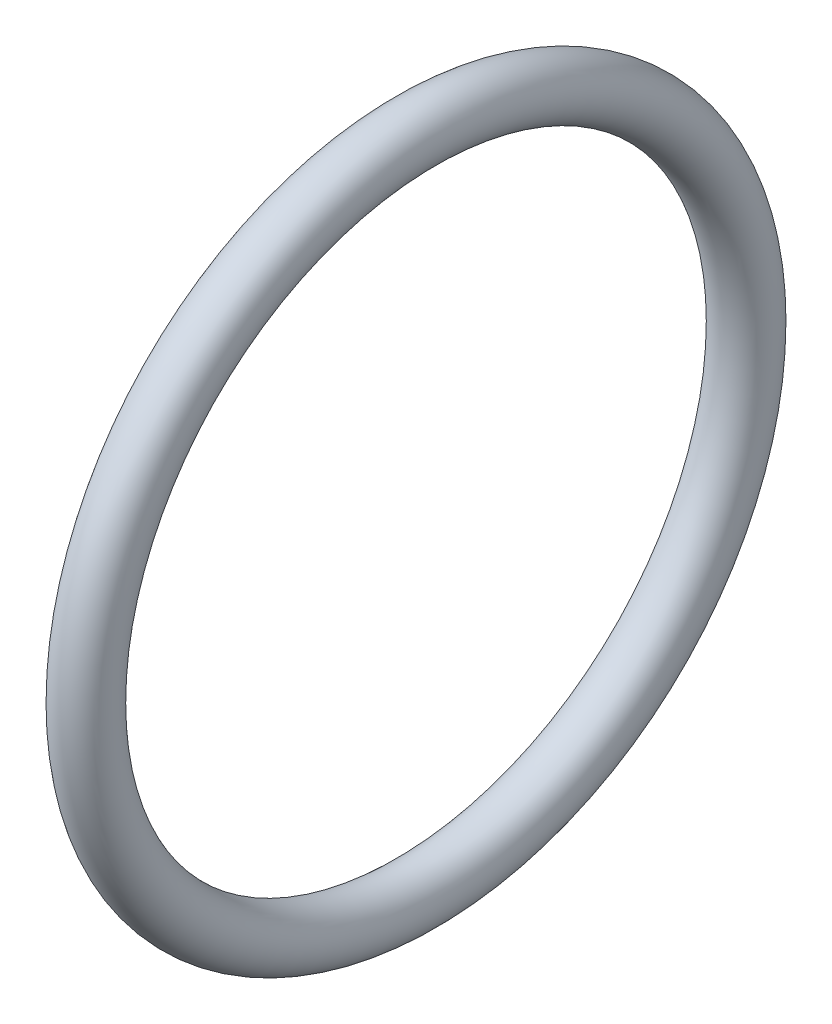
SolidWorks part; units mm, degrees
ref_plane "Front Plane" through (0, 0, 0) normal (0, 0, 1) x (1, 0, 0)
ref_plane "Top Plane" through (0, 0, 0) normal (0, 1, 0) x (1, 0, 0)
ref_plane "Right Plane" through (0, 0, 0) normal (1, 0, 0) x (0, 0, -1)
sketch "Sketch2" plane through (0, 0, 0) normal (0, 0, 1) x (1, 0, 0)
  line L0 (0, 0) -> (58.591, 0) construction
  line L2 (0, 0) -> (18.4, 0)
  line L3 (0, 0) -> (0, 2.5)
  line L4 (0, 2.5) -> (18.4, 2.5)
  line L5 (18.4, 0) -> (18.4, 2.5)
  line L6 (6, 2.5) -> (6, 6)
  line L11 (6, 6) -> (9.97, 6)
  line L16 (12.97, 6) -> (12.97, 3)
  line L17 (12.97, 3) -> (13.6304, 3)
  line L18 (13.6304, 3) -> (13.6304, 2.5)
  line L19 (13.6304, 2.5) -> (6, 2.5)
  line L22 (13.6304, 2.5) -> (16.1104, 2.5)
  line L23 (13.6304, 2.5) -> (13.6304, 4)
  line L24 (13.6304, 4) -> (16.1104, 4)
  line L25 (16.1104, 2.5) -> (16.1104, 4)
  line L27 (6, 6) -> (9.97, 6)
  line L28 (6, 6) -> (6, 9)
  line L29 (6, 9) -> (9.97, 9)
  line L30 (9.97, 6) -> (9.97, 9)
  line L31 (6, 9) -> (6, 8.25)
  line L32 (6, 8.25) -> (5, 8.25)
  line L33 (8.58, 22.001) -> (8.58, 12.476) construction
  line L34 (5, 12.476) -> (12.16, 12.476)
  line L35 (9.97, 9) -> (12.16, 9)
  line L36 (5, 7.5) -> (3, 7.5)
  line L37 (5, 8.25) -> (5, 12.476)
  line L38 (5, 7.5) -> (5, 14)
  line L39 (5, 14) -> (3, 14)
  line L40 (3, 7.5) -> (3, 14)
  line L41 (5, 22.001) -> (12.16, 22.001)
  line L42 (5, 22.001) -> (5, 30.1625)
  line L43 (5, 30.1625) -> (12.16, 30.1625)
  line L44 (12.16, 22.001) -> (12.16, 30.1625)
  line L49 (16.6304, 22.001) -> (16.6304, 7.5)
  line L51 (23.0104, 7.5) -> (23.0104, 6.5)
  line L54 (16.1104, 4) -> (13.6304, 4)
  line L56 (18.0304, 7.5) -> (23.0104, 7.5)
  line L57 (13.16, 22.001) -> (16.6304, 22.001)
  line L58 (16.1104, 3.5) -> (20.0104, 3.5)
  line L59 (29.9004, 14) -> (26.9004, 11)
  line L60 (4, 31.75) -> (18.0304, 31.75)
  line L61 (18.0304, 7.5) -> (23.0104, 7.5)
  line L62 (18.0304, 7.5) -> (18.0304, 12)
  line L63 (18.0304, 12) -> (23.0104, 12)
  line L64 (23.0104, 7.5) -> (23.0104, 12)
  line L65 (18.0304, 31.75) -> (18.0304, 12)
  line L66 (23.0104, 11) -> (26.9004, 11)
  line L67 (34.8004, 23) -> (31.3004, 19.5)
  line L68 (35.8004, 31) -> (38.7904, 33.99)
  line L69 (29.9004, 14) -> (29.9004, 15)
  line L70 (29.9004, 15) -> (22.9304, 15)
  line L71 (22.9304, 15) -> (21.0304, 15)
  line L72 (18.0304, 7.5) -> (16.6304, 7.5)
  line L73 (21.0304, 15) -> (21.0304, 43)
  line L74 (20.0304, 40) -> (10.0704, 40)
  line L75 (10.0704, 40) -> (4, 40)
  line L76 (21.0304, 43) -> (20.0304, 43)
  line L77 (22.9304, 15) -> (29.9004, 15)
  line L78 (22.9304, 15) -> (22.9304, 21)
  line L79 (22.9304, 21) -> (29.9004, 21)
  line L80 (29.9004, 15) -> (29.9004, 21)
  line L81 (10.0704, 40) -> (20.0304, 40)
  line L82 (10.0704, 40) -> (10.0704, 50)
  line L83 (10.0704, 50) -> (20.0304, 50)
  line L84 (20.0304, 40) -> (20.0304, 50)
  line L85 (4, 40) -> (4, 31.75)
  line L86 (12.97, 3) -> (12.97, 2.5)
  line L87 (31.3004, 19.5) -> (29.9004, 19.5)
  line L88 (21.51, 63.5) -> (21.51, 44)
  line L89 (21.51, 63.5) -> (25.9304, 63.5)
  line L90 (25.9304, 63.5) -> (25.9304, 25)
  line L91 (27.8304, 25) -> (25.9304, 25)
  line L92 (10.0704, 48) -> (9, 48)
  line L93 (9, 48) -> (9, 53.476)
  line L94 (9, 53.476) -> (20.0304, 53.476)
  line L95 (20.0304, 53.476) -> (20.0304, 50)
  line L96 (14.5152, 63.001) -> (14.5152, 53.476) construction
  line L97 (9, 63.001) -> (20.0304, 63.001)
  line L98 (9, 63.001) -> (9, 68.2625)
  line L99 (9, 68.2625) -> (20.0304, 68.2625)
  line L100 (20.0304, 63.001) -> (20.0304, 68.2625)
  line L101 (12.97, 6) -> (11.97, 6)
  line L102 (9, 42.5) -> (5, 42.5)
  line L103 (9, 42.5) -> (9, 55)
  line L104 (9, 55) -> (5, 55)
  line L105 (5, 42.5) -> (5, 55)
  line L106 (9.97, 6) -> (10.87, 6)
  line L107 (27.8304, 25) -> (34.8004, 25)
  line L108 (34.8004, 25) -> (34.8004, 23)
  line L109 (0, 0) -> (-2, 0)
  line L110 (0, 0) -> (0, 11)
  line L111 (27.8304, 25) -> (34.8004, 25)
  line L112 (27.8304, 25) -> (27.8304, 32.5)
  line L113 (27.8304, 32.5) -> (34.8004, 32.5)
  line L114 (34.8004, 25) -> (34.8004, 32.5)
  line L115 (35.8004, 31) -> (34.8004, 31)
  line L116 (27.8304, 32.5) -> (27.8304, 64.5)
  line L117 (21.1827, 74.025) -> (6.8477, 74.025)
  line L118 (6.8477, 74.025) -> (6.8477, 76.2)
  line L119 (38.7904, 47.29) -> (30.8304, 55.25)
  line L120 (0, 11) -> (-2, 11)
  line L121 (38.7904, 43.815) -> (30.8529, 43.815)
  line L123 (-4.8, 69.85) -> (1.55, 76.2)
  line L124 (38.7904, 47.29) -> (38.7904, 33.99)
  line L125 (-2, 0) -> (-2, 11)
  line L126 (38.7904, 37.465) -> (30.8529, 37.465)
  line L127 (30.8529, 43.815) -> (30.8529, 37.465)
  line L128 (6, 2.5) -> (6, 0)
  line L129 (0, 63.5) -> (0, 30)
  line L132 (5, 63.5) -> (0, 63.5)
  line L136 (-1.8, 30) -> (-11.76, 30)
  line L138 (-13.76, 25.4) -> (-2, 25.4)
  line L139 (-2, 25.4) -> (-2, 11.5)
  line L140 (27.8304, 64.5) -> (21.1827, 64.5)
  line L141 (-1.8, 30) -> (-11.76, 30)
  line L142 (-1.8, 30) -> (-1.8, 39)
  line L143 (-1.8, 39) -> (-11.76, 39)
  line L144 (-11.76, 30) -> (-11.76, 39)
  line L145 (21.1827, 64.5) -> (21.1827, 74.025)
  line L146 (-12.76, 37) -> (-12.76, 47.29)
  line L147 (-12.76, 37) -> (-11.76, 37)
  line L148 (30.8304, 55.25) -> (30.8304, 76.2)
  line L149 (11.97, 6) -> (11.97, 5.45)
  line L154 (-2, 11.5) -> (1, 11.5)
  line L155 (5, 60.6197) -> (24.05, 60.6197)
  line L160 (5, 60.6197) -> (5, 55.8572)
  line L161 (5, 55.8572) -> (24.05, 55.8572)
  line L166 (24.05, 60.6197) -> (24.05, 55.8572)
  line L167 (5, 60.6197) -> (24.05, 55.8572) construction
  line L172 (5, 55.8572) -> (24.05, 60.6197) construction
  line L173 (24.05, 62.2072) -> (25.9304, 62.2072)
  line L174 (11.97, 5.45) -> (10.87, 5.45)
  line L175 (10.87, 6) -> (10.87, 5.45)
  line L176 (24.05, 62.2072) -> (24.05, 54.2697)
  line L177 (24.05, 54.2697) -> (25.9304, 54.2697)
  line L178 (25.9304, 62.2072) -> (25.9304, 54.2697)
  line L179 (24.05, 62.2072) -> (25.9304, 54.2697) construction
  line L180 (24.05, 54.2697) -> (25.9304, 62.2072) construction
  line L181 (3, 19.6197) -> (15.7, 19.6197)
  line L182 (3, 19.6197) -> (3, 14.8572)
  line L183 (3, 14.8572) -> (15.7, 14.8572)
  line L184 (15.7, 19.6197) -> (15.7, 14.8572)
  line L185 (3, 19.6197) -> (15.7, 14.8572) construction
  line L186 (3, 14.8572) -> (15.7, 19.6197) construction
  line L187 (15.7, 21.2072) -> (16.6304, 21.2072)
  line L188 (15.7, 21.2072) -> (15.7, 13.2697)
  line L189 (15.7, 13.2697) -> (16.6304, 13.2697)
  line L190 (16.6304, 21.2072) -> (16.6304, 13.2697)
  line L191 (15.7, 21.2072) -> (16.6304, 13.2697) construction
  line L192 (15.7, 13.2697) -> (16.6304, 21.2072) construction
  line L193 (1, 11.5) -> (1, 6.5)
  line L194 (1, 6.5) -> (3, 6.5)
  line L195 (23.0104, 6.5) -> (20.0104, 3.5)
  line L196 (5, 63.5) -> (5, 42.5)
  line L197 (5, 42.5) -> (3, 42.5)
  line L198 (3, 42.5) -> (3, 6.5)
  line L199 (6, 0) -> (12.97, 0)
  line L200 (12.97, 0) -> (12.97, 2.5)
  line L201 (18.0304, 31.75) -> (18.0304, 35.875)
  line L202 (18.0304, 35.875) -> (21.0304, 35.875)
  line L203 (30.8304, 76.2) -> (6.8477, 76.2)
  line L204 (3.4027, 69.85) -> (7.8477, 69.85) construction
  line L205 (7.8477, 67.4687) -> (26.8977, 67.4688)
  line L206 (7.8477, 74.025) -> (7.8477, 64.5)
  line L207 (7.8477, 64.5) -> (-1.8, 64.5)
  line L208 (-1.8, 64.5) -> (-1.8, 39)
  line L209 (-12.76, 47.29) -> (-4.8, 55.25)
  line L210 (-4.8, 55.25) -> (-4.8, 69.85)
  line L211 (7.8477, 67.4687) -> (7.8477, 72.2313)
  line L212 (7.8477, 72.2313) -> (26.8977, 72.2313)
  line L213 (26.8977, 67.4688) -> (26.8977, 72.2313)
  line L214 (26.8977, 73.8187) -> (30.8304, 73.8187)
  line L215 (26.8977, 73.8187) -> (26.8977, 65.8813)
  line L216 (26.8977, 65.8813) -> (30.8304, 65.8813)
  line L217 (30.8304, 73.8187) -> (30.8304, 65.8813)
  line L218 (3.4027, 72.2313) -> (25.6277, 72.2313)
  line L219 (3.4027, 72.2313) -> (3.4027, 67.4687)
  line L220 (3.4027, 67.4687) -> (25.6277, 67.4687)
  line L221 (25.6277, 72.2313) -> (25.6277, 67.4687)
  line L222 (25.6277, 69.85) -> (21.1827, 69.85) construction
  line L223 (21.51, 44) -> (22.9304, 44)
  line L224 (22.9304, 44) -> (22.9304, 21)
  line L225 (13.6304, 4) -> (13.6304, 12.2697)
  line L226 (13.6304, 12.2697) -> (13.16, 12.2697)
  line L227 (13.16, 12.2697) -> (13.16, 22.001)
  line L228 (12.16, 9) -> (12.16, 12.476)
  line L229 (-1.8, 30) -> (0, 30)
  line L230 (9, 65.6317) -> (3.4027, 65.6317) construction
  line L231 (20.0304, 65.6317) -> (25.6277, 65.6317) construction
  line L232 (1.55, 76.2) -> (6.8477, 76.2)
  line L233 (-11.76, 30) -> (-13.76, 30)
  line L234 (-13.76, 30) -> (-13.76, 25.4)
  circle A0 centre (26.8804, 25.95) radius 0.95
  circle A1 centre (21.9804, 15.95) radius 0.95
  circle A2 centre (17.3304, 8.2) radius 0.7
  circle A3 centre (10.42, 6.45) radius 0.45
  circle A4 centre (-0.9, 30.9) radius 0.9
  point P7 (24.9902, 58.2385)
  point P131 (16.1652, 17.2385)
  point P135 (14.525, 58.2385)
  point P146 (9.35, 17.2385)
sketch "Sketch3" plane through (0, 0, 0) normal (0, 0, 1) x (1, 0, 0)
  circle A0 centre (17.3304, 8.2) radius 0.7 construction
  circle A1 centre (17.3304, 8.2) radius 0.7
revolve "Revolve1" add sketch "Sketch3" angle 360 about L0
